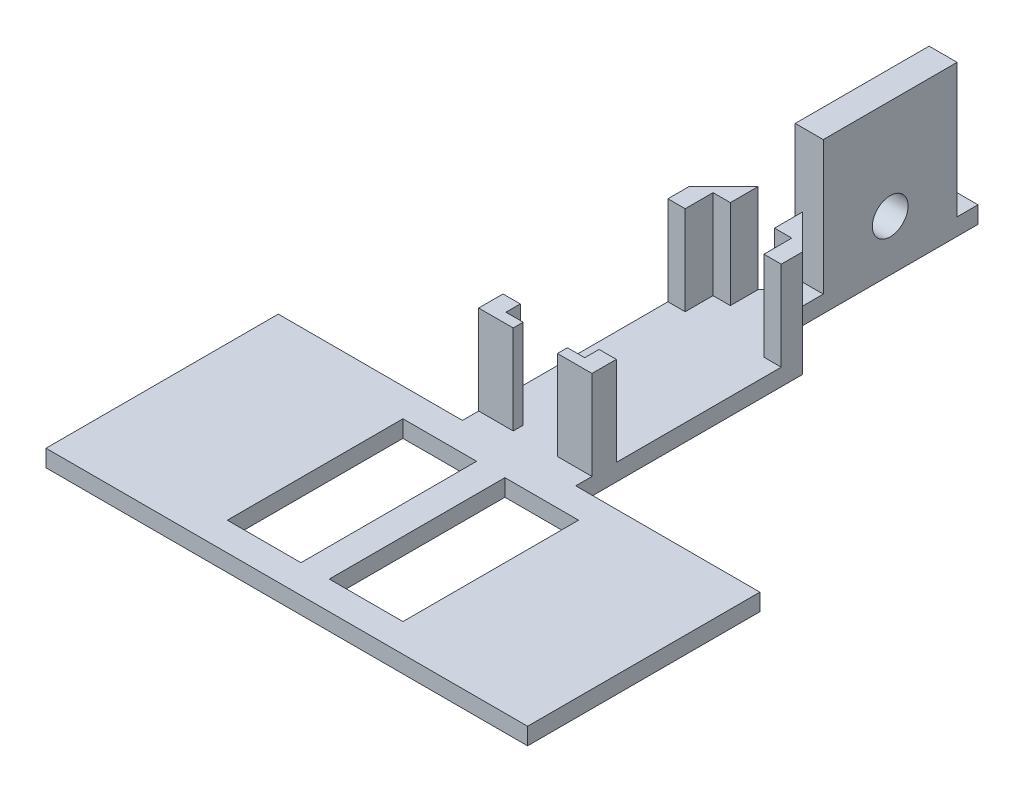
SolidWorks part; units mm, degrees
ref_plane "Front Plane" through (0, 0, 0) normal (0, 0, 1) x (1, 0, 0)
ref_plane "Top Plane" through (0, 0, 0) normal (0, 1, 0) x (1, 0, 0)
ref_plane "Right Plane" through (0, 0, 0) normal (1, 0, 0) x (0, 0, -1)
sketch "Sketch1" plane through (0, 0, 0) normal (0, 1, 0) x (1, 0, 0)
  line L0 (-53.975, 20.6803) -> (-53.975, -31.3897)
  line L1 (-3.175, 14.3303) -> (-3.175, -25.0397)
  line L3 (-19.685, 14.3303) -> (-19.685, -25.0397)
  line L4 (-19.685, -25.0397) -> (-3.175, -25.0397)
  line L8 (-19.685, 14.3303) -> (-3.175, 14.3303)
  line L9 (3.175, 14.3303) -> (19.685, 14.3303)
  line L10 (-53.975, -31.3897) -> (53.975, -31.3897)
  line L11 (-12.7, 20.6803) -> (-12.7, 71.4803)
  line L13 (12.7, 20.6803) -> (12.7, 71.4803)
  line L14 (53.975, 20.6803) -> (53.975, -31.3897)
  line L15 (-12.7, 71.4803) -> (-3.0567, 81.1236)
  line L16 (12.7, 71.4803) -> (3.2252, 80.9551)
  line L17 (19.685, -25.0397) -> (3.175, -25.0397)
  line L18 (19.685, 14.3303) -> (19.685, -25.0397)
  line L20 (3.175, 14.3303) -> (3.175, -25.0397)
  line L21 (3.2252, 80.9551) -> (3.2252, 120.3251)
  line L23 (-3.0567, 81.1236) -> (-3.0567, 120.3251)
  line L24 (-3.0567, 120.3251) -> (3.2252, 120.3251)
  line L37 (-53.975, 20.6803) -> (-12.7, 20.6803)
  line L41 (53.975, 20.6803) -> (12.7, 20.6803)
  point P16 (-12.7, 46.0803)
  point P39 (12.7, 46.0803)
  dimension "D1" = 39.37
  dimension "D2" = 3.175
  dimension "D3" = 16.51
  dimension "D4" = 6.35
  dimension "D5" = 50.8
  dimension "D6" = 6.2818
  dimension "D7" = 39.37
  dimension "D8" = 12.7
  dimension "D9" = 6.35
  dimension "D10" = 3.175
  dimension "D11" = 6.35
  dimension "D12" = 34.29
  dimension "D13" = 39.37
  dimension "D14" = 16.51
  dimension "D15" = 34.29
extrude "Boss-Extrude1" add sketch "Sketch1" along normal blind 3.81
sketch "Sketch2" plane through (0, 3.81, 0) normal (0, 1, 0) x (1, 0, 0)
  line L0 (-3.0567, 115.6401) -> (3.2252, 115.6401)
  line L1 (-3.0567, 120.3251) -> (-3.0567, 81.1236) construction
  line L2 (3.2252, 80.9551) -> (3.2252, 120.3251) construction
  line L3 (3.2252, 115.6401) -> (3.2252, 85.6401)
  line L4 (3.2252, 85.6401) -> (-3.0567, 85.6401)
  line L5 (-3.0567, 85.6401) -> (-3.0567, 115.6401)
  line L6 (3.2252, 120.3251) -> (-3.0567, 120.3251) construction
  point P10 (3.2252, 100.6401)
  dimension "D1" = 30
  dimension "D2" = 19.685
extrude "Boss-Extrude2" add sketch "Sketch2" along normal blind 30
sketch "Sketch3" plane through (3.2252, 0, 0) normal (1, 0, 0) x (0, 0, -1)
  line L0 (115.6401, 33.81) -> (115.6401, 3.81) construction
  line L1 (85.6401, 33.81) -> (85.6401, 3.81) construction
  circle A0 centre (100.6401, 11.43) radius 4
  point P7 (85.6401, 15.8802)
  dimension "D1" = 8
  dimension "D2" = 30
extrude "Cut-Extrude1" cut sketch "Sketch3" against normal up to next
sketch "Sketch6" plane through (0, 3.81, 0) normal (0, 1, 0) x (1, 0, 0)
  line L0 (-8.128, 24.3194) -> (-4.953, 24.3194)
  line L1 (-4.953, 24.3194) -> (-4.953, 26.5616)
  line L2 (-4.953, 26.5616) -> (-8.8291, 26.5616)
  line L3 (-8.8291, 26.5616) -> (-8.8291, 29.7795)
  line L4 (-8.8291, 29.7795) -> (-12.7, 29.7795)
  line L5 (-12.7, 29.7795) -> (-12.7, 24.3194)
  line L6 (-12.7, 24.3194) -> (-8.128, 24.3194)
  line L7 (-12.7, 71.4803) -> (-12.7, 20.6803) construction
  line L8 (0, 0) -> (0, 73.7144) construction
  line L9 (12.7, 24.3194) -> (8.128, 24.3194)
  line L10 (12.7, 29.7795) -> (12.7, 24.3194)
  line L11 (8.8291, 29.7795) -> (12.7, 29.7795)
  line L12 (8.8291, 26.5616) -> (8.8291, 29.7795)
  line L13 (4.953, 26.5616) -> (8.8291, 26.5616)
  line L14 (4.953, 24.3194) -> (4.953, 26.5616)
  line L15 (8.128, 24.3194) -> (4.953, 24.3194)
  line L16 (12.7, 46.0803) -> (-12.7, 46.0803) construction
  line L17 (12.7, 20.6803) -> (12.7, 71.4803) construction
  line L32 (-4.953, 24.3194) -> (-4.953, 86.2587) construction
  line L33 (-8.8291, 26.5616) -> (-8.8291, 87.1413) construction
  line L34 (-4.953, 79.2273) -> (-12.7, 71.4803)
  line L35 (-3.0567, 81.1236) -> (-12.7, 71.4803) construction
  line L36 (-4.953, 72.9887) -> (-8.8291, 72.9887)
  line L37 (-8.8291, 72.9887) -> (-8.8291, 66.743)
  line L38 (-8.8291, 66.743) -> (-12.7, 66.743)
  line L39 (-12.7, 66.743) -> (-12.7, 71.4803)
  line L40 (-4.953, 72.9887) -> (-4.953, 79.2273)
  line L41 (4.953, 72.9887) -> (4.953, 79.2273)
  line L42 (12.7, 66.743) -> (12.7, 71.4803)
  line L43 (8.8291, 66.743) -> (12.7, 66.743)
  line L44 (8.8291, 72.9887) -> (8.8291, 66.743)
  line L45 (4.953, 72.9887) -> (8.8291, 72.9887)
  line L46 (4.953, 79.2273) -> (12.7, 71.4803)
  point P26 (-8.8291, 72.9887)
extrude "Boss-Extrude3" add sketch "Sketch6" along normal blind 20
